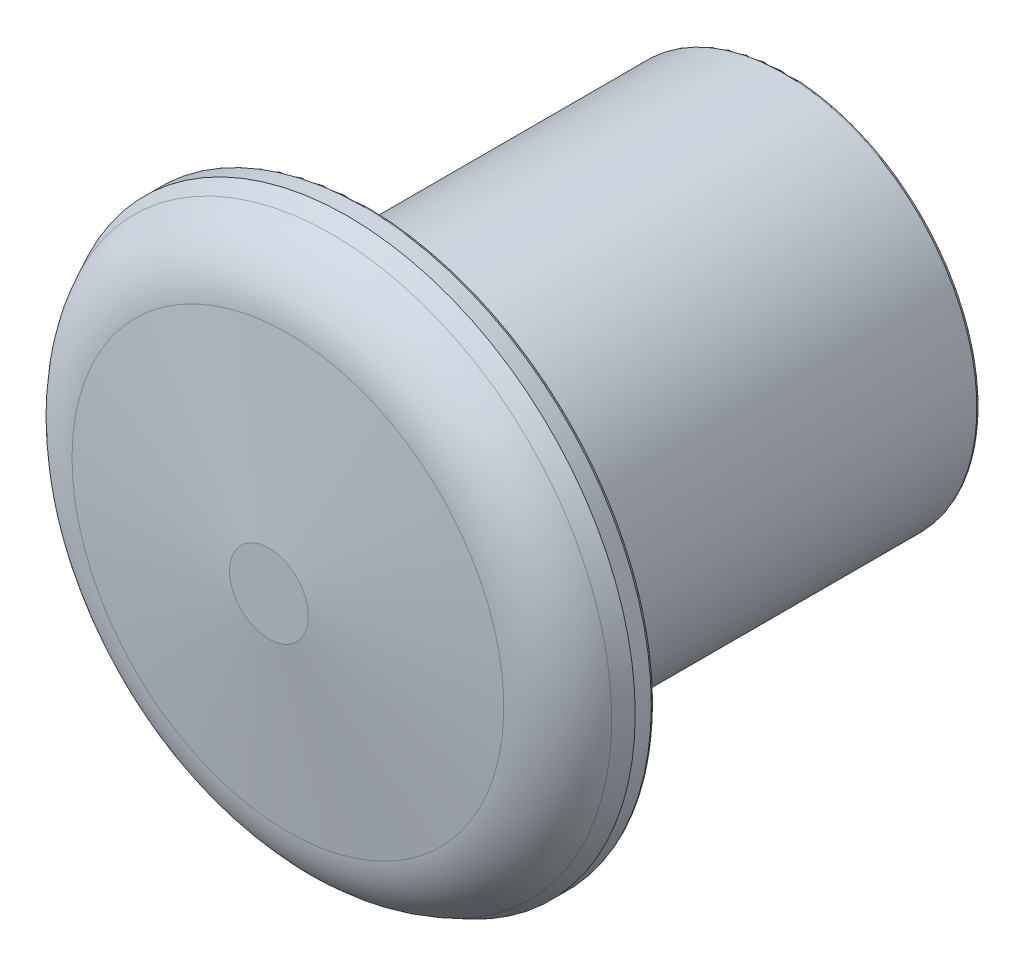
SolidWorks part; units mm, degrees
ref_plane "Front Plane" through (0, 0, 0) normal (0, 0, 1) x (1, 0, 0)
ref_plane "Top Plane" through (0, 0, 0) normal (0, 1, 0) x (1, 0, 0)
ref_plane "Right Plane" through (0, 0, 0) normal (1, 0, 0) x (0, 0, -1)
sketch "Sketch1" plane through (0, 0, 0) normal (1, 0, 0) x (0, 0, -1)
  line L0 (0, 0) -> (0, 10.95) construction
  line L1 (0, 10.95) -> (3, 10.95) construction
  line L3 (2.3972, 10.656) -> (3, 10.95)
  line L4 (3, 10.95) -> (3.7122, 10.95)
  line L5 (3.7122, 10.95) -> (3.7122, 8.9)
  line L6 (3.7122, 8.9) -> (4.7122, 8.9)
  line L7 (4.7122, 8.9) -> (4.7122, 7.35)
  line L8 (4.7122, 7.35) -> (19.7122, 7.35)
  line L11 (0, 0) -> (0, 1.5)
  line L12 (0, 1.5) -> (0.7238, 8.2226)
  line L13 (19.7122, 7.35) -> (19.7122, 6.35)
  line L14 (19.7122, 6.35) -> (3, 6.35)
  line L18 (1.8825, 0) -> (0, 0)
  line L19 (3, 6.35) -> (1.8825, 6.35)
  line L20 (1.8825, 6.35) -> (1.8825, 0)
  arc A0 (0.7238, 8.2226) -> (2.3972, 10.656) centre (3.7122, 7.9596) cw
  point P7 (0, 0)
  dimension "D3" = 3
  dimension "D1" = 10.95
  dimension "D2" = 3
  dimension "D4" = 2.05
  dimension "D5" = 1
  dimension "D6" = 1.55
  dimension "D7" = 15
  dimension "D8" = 1
revolve "Revolve2" add sketch "Sketch1" angle 360 about L18
fillet "Fillet3" radius 0.1 3 edges at (-10.95, 0, -3.7122) (-8.9, 0, -4.7122) (-7.35, 0, -19.7122)
fillet "Fillet4" radius 0.1 1 edges at (-6.35, 0, -19.7122)
